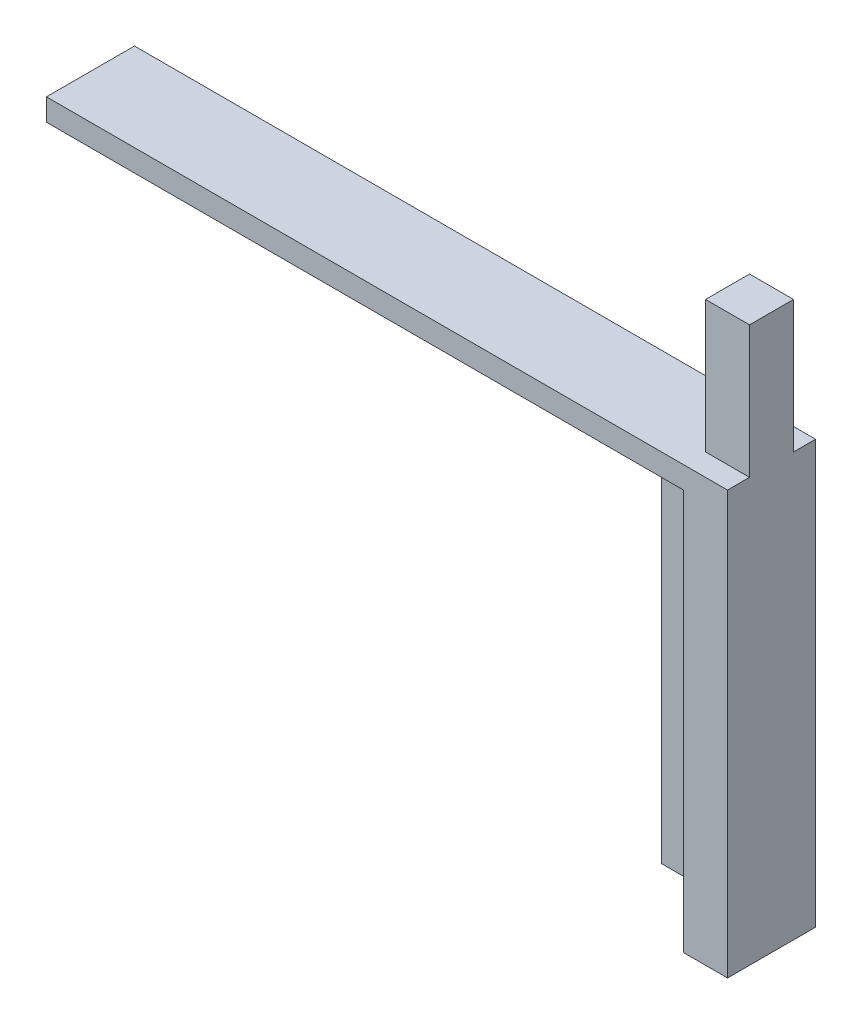
SolidWorks part; units mm, degrees
ref_plane "Front Plane" through (0, 0, 0) normal (0, 0, 1) x (1, 0, 0)
ref_plane "Top Plane" through (0, 0, 0) normal (0, 1, 0) x (1, 0, 0)
ref_plane "Right Plane" through (0, 0, 0) normal (1, 0, 0) x (0, 0, -1)
sketch "Sketch3" plane through (0, 0, 0) normal (0, 0, 1) x (1, 0, 0)
  line L0 (0, 0) -> (0, -5)
  line L1 (0, -5) -> (20, -5)
  line L2 (20, -5) -> (20, -25)
  line L3 (0, 0) -> (20, 0)
  line L4 (20, 0) -> (20, 30)
  line L5 (20, 30) -> (30, 30)
  line L6 (30, 30) -> (30, -25)
  line L7 (30, -25) -> (20, -25)
  dimension "D1" = 20
  dimension "D2" = 20
  dimension "D3" = 20
  dimension "D4" = 5
  dimension "D5" = 10
  dimension "D6" = 55
extrude "Boss-Extrude3" add sketch "Sketch3" along normal blind 10
sketch "Sketch4" plane through (0, 0, 0) normal (0, 0, -1) x (-1, 0, 0)
  line L5 (0, 0) -> (-30, 0)
  line L6 (0, 0) -> (0, -25)
  line L7 (0, -25) -> (-30, -25)
  line L8 (-30, 0) -> (-30, -25)
extrude "Boss-Extrude4" add sketch "Sketch4" along normal blind 5
sketch "Sketch5" plane through (0, 0, 10) normal (0, 0, 1) x (1, 0, 0)
  line L0 (0, 0) -> (0, -5)
  line L1 (0, -5) -> (20, -5)
  line L2 (20, -5) -> (20, -25)
  line L3 (20, -25) -> (30, -25)
  line L4 (30, -25) -> (30, 0)
  line L5 (30, 0) -> (0, 0)
extrude "Boss-Extrude5" add sketch "Sketch5" along normal blind 5
sketch "Sketch6" plane through (0, -25, 0) normal (0, -1, 0) x (1, 0, 0)
  line L0 (20, 15) -> (20, 0)
  line L1 (20, 0) -> (30, 0) construction
  line L2 (20, 0) -> (0, 0)
  line L3 (0, 0) -> (0, -5)
  line L4 (0, -5) -> (30, -5)
  line L5 (30, -5) -> (30, 15)
  line L6 (30, 15) -> (20, 15)
extrude "Boss-Extrude6" add sketch "Sketch6" along normal up to surface (71 mm away)
sketch "Sketch7" plane through (0, 0, 0) normal (-1, 0, 0) x (0, 0, 1)
  line L0 (-5, -96) -> (-5, 0) construction
  line L1 (15, 0) -> (-5, 0)
  line L2 (15, 0) -> (15, -5)
  line L3 (15, -5) -> (0, -5)
  line L4 (-5, 0) -> (-5, -5)
  line L6 (-5, -9.319) -> (0, -9.319)
  line L7 (-5, -9.319) -> (-5, 0)
  line L8 (-5, 0) -> (0, 0)
  line L9 (0, -9.319) -> (0, -5)
  line M1 (15, 0) -> (-5, 0)
  line M2 (-5, 0) -> (-5, -96)
  line M4 (0, -96) -> (0, -5)
  line M5 (0, -5) -> (15, -5)
  line M6 (15, -5) -> (15, 0)
extrude "Boss-Extrude7" add sketch "Sketch7" along normal blind 124.7205 contours L6 L1 M2 M4 M5 M6 M1 region at (0, -3.3275, 3.668)
